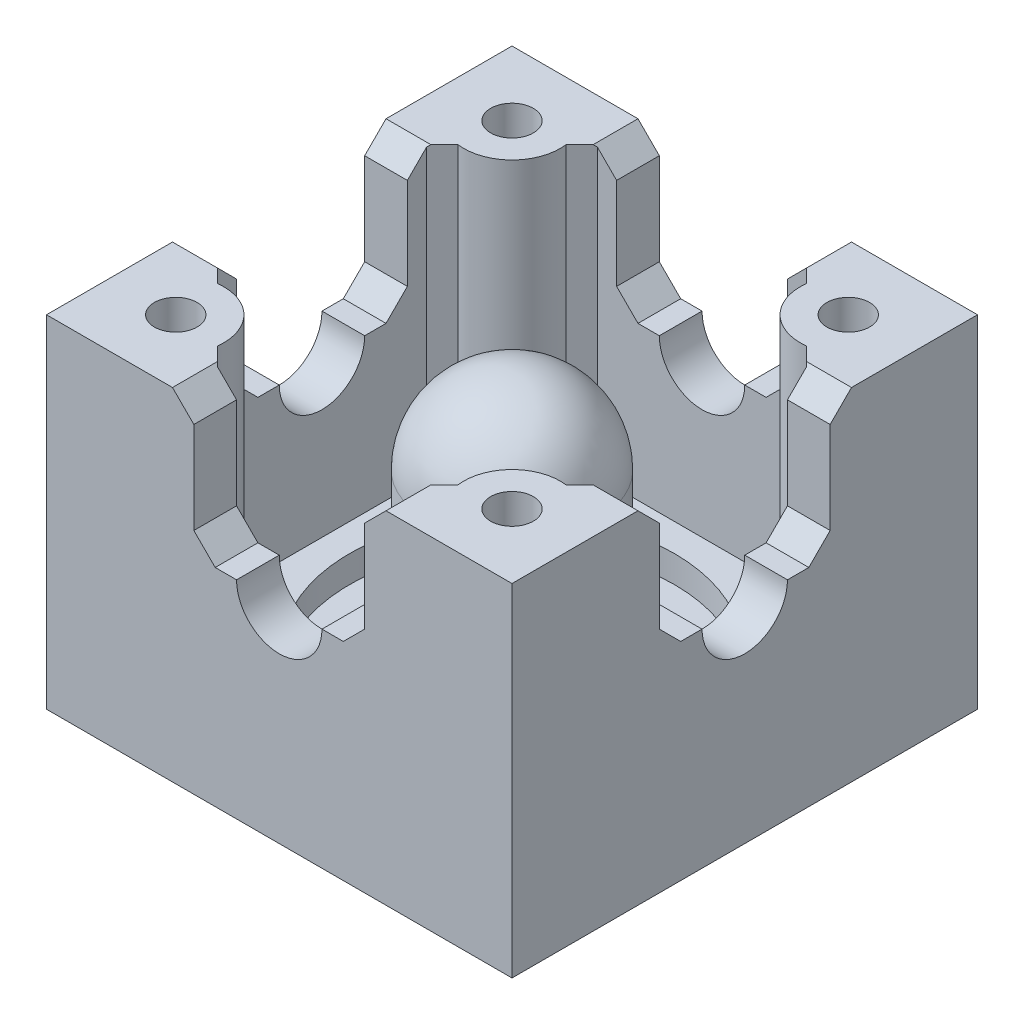
SolidWorks part; units mm, degrees
ref_plane "Front Plane" through (0, 0, 0) normal (0, 0, 1) x (1, 0, 0)
ref_plane "Top Plane" through (0, 0, 0) normal (0, 1, 0) x (1, 0, 0)
ref_plane "Right Plane" through (0, 0, 0) normal (1, 0, 0) x (0, 0, -1)
sketch "Sketch1" plane through (0, 0, 0) normal (0, 1, 0) x (1, 0, 0)
  line L1 (0, 0) -> (13.843, 0)
  line L2 (0, 0) -> (0, 13.843)
  line L3 (0, 13.843) -> (13.843, 13.843)
  line L4 (13.843, 0) -> (13.843, 13.843)
  dimension "D1" = 13.843
  dimension "D2" = 13.843
extrude "main body extrude" add sketch "Sketch1" along normal blind 10.16
sketch "Sketch4" plane through (0, 10.16, 0) normal (0, 1, 0) x (1, 0, 0)
  line L0 (0, 13.843) -> (13.843, 0) construction
  line L1 (13.843, 0) -> (13.843, 13.843) construction
  line L2 (1.27, 10.033) -> (3.81, 12.573)
  line L7 (13.843, 13.843) -> (0, 13.843) construction
  line L8 (3.81, 1.27) -> (10.033, 1.27)
  line L9 (10.033, 12.573) -> (12.573, 10.033)
  line L10 (0, 0) -> (13.843, 0) construction
  line L15 (1.27, 3.81) -> (1.27, 10.033)
  line L16 (3.81, 12.573) -> (10.033, 12.573)
  line L17 (12.573, 3.81) -> (12.573, 10.033)
  line L18 (1.27, 1.27) -> (12.573, 12.573) construction
  line L19 (1.27, 12.573) -> (12.573, 1.27) construction
  line L20 (10.033, 1.27) -> (12.573, 3.81)
  line L21 (1.27, 3.81) -> (3.81, 1.27)
  circle A0 centre (1.9215, 11.9215) radius 0.635
  circle A1 centre (11.9215, 11.9215) radius 0.635
  circle A2 centre (11.9215, 1.9215) radius 0.635
  circle A3 centre (1.9215, 1.9215) radius 0.635
  circle A4 centre (1.9215, 11.9215) radius 1.435
  circle A5 centre (11.9215, 11.9215) radius 1.435
  circle A6 centre (11.9215, 1.9215) radius 1.435
  circle A7 centre (1.9215, 1.9215) radius 1.435
  point P5 (6.9215, 6.9215)
  point P6 (6.9215, 6.9215)
  point P27 (6.9215, 6.9215)
  point P28 (6.9215, 6.9215)
  point P44 (6.9215, 6.9215)
  dimension "D3" = 1.27
  dimension "D6" = 0.8
  dimension "D1" = 1.27
  dimension "D2" = 1.27
  dimension "D5" = 10
  dimension "D4" = 4
  dimension "D7" = 4
extrude "main body cut" cut sketch "Sketch4" against normal offset from surface (9.36 mm away) 0.8 contours L8 region at (6.9215, 10.16, -6.9215) up to face at (6.9215, 0, -6.9215)
sketch "Sketch21" plane through (0, 10.16, 0) normal (0, 1, 0) x (1, 0, 0)
  line L0 (0, 13.843) -> (13.843, 0) construction
  circle A0 centre (1.9215, 11.9215) radius 0.635
  circle A1 centre (11.9215, 11.9215) radius 0.635
  circle A2 centre (11.9215, 1.9215) radius 0.635
  circle A3 centre (1.9215, 1.9215) radius 0.635
  point P7 (6.9215, 6.9215)
  point P17 (6.9215, 6.9215)
  dimension "D2" = 1.27
  dimension "D1" = 4
extrude "screw holes cut" cut sketch "Sketch21" against normal through all
sketch "Sketch5" plane through (0, 0, 0) normal (0, 0, 1) x (1, 0, 0)
  line L0 (6.9215, 12.7116) -> (6.9215, 6.1595) construction
  line L1 (8.1915, 12.7116) -> (8.1915, 6.1595)
  line L2 (0, 10.16) -> (13.843, 10.16) construction
  line L3 (5.6515, 12.7116) -> (5.6515, 6.1595)
  line L4 (6.9215, 6.1595) -> (6.9215, 2.6781) construction
  line L5 (4.3815, 12.7116) -> (9.4615, 12.7116)
  line L6 (4.3815, 12.7116) -> (4.3815, 6.1595)
  line L7 (4.3815, 6.1595) -> (9.4615, 6.1595)
  line L8 (9.4615, 12.7116) -> (9.4615, 6.1595)
  line L9 (4.3815, 12.7116) -> (9.4615, 6.1595) construction
  line L10 (4.3815, 6.1595) -> (9.4615, 12.7116) construction
  line L19 (11.811, 5.207) -> (10.541, 5.207)
  line L20 (2.032, 8.509) -> (3.302, 8.509)
  line L21 (2.032, 8.509) -> (2.032, 5.207)
  line L22 (2.032, 5.207) -> (3.302, 5.207)
  line L23 (3.302, 8.509) -> (3.302, 5.207)
  line L24 (10.541, 8.509) -> (10.541, 5.207)
  line L25 (11.811, 8.509) -> (10.541, 8.509)
  line L26 (11.811, 8.509) -> (11.811, 5.207)
  arc A1 (8.1915, 12.7116) -> (5.6515, 12.7116) centre (6.9215, 12.7116) ccw
  arc A2 (5.6515, 6.1595) -> (8.1915, 6.1595) centre (6.9215, 6.1595) ccw
  circle A3 centre (6.9215, 6.1595) radius 1.27 construction
  point P2 (6.9215, 10.16)
  point P3 (6.9215, 9.4356)
  point P14 (6.9215, 9.4356)
  line M8 (13.843, 10.16) -> (0, 10.16)
  dimension "D1" = 2.54
  dimension "D2" = 4.0005
  dimension "D3" = 5.08
  dimension "D4" = 1.27
  dimension "D5" = 3.302
  dimension "D6" = 7.239
  dimension "D7" = 1.651
extrude "x axis slot" cut sketch "Sketch5" against normal through all contours L6 L7 L3 M8 | L3 L7 L1 M8 | L8 L1 L7 M8 | L7 A2 region at (8.8265, 8.1598, 0) region at (6.9215, 8.1598, 0) region at (6.9215, 5.6205, 0) region at (5.0165, 8.1598, 0)
sketch "Sketch6" plane through (13.843, 0, 0) normal (1, 0, 0) x (0, 0, -1)
  line L0 (0, 10.16) -> (13.843, 10.16) construction
  line L1 (6.9215, 6.1595) -> (6.9215, 12.6452) construction
  line L2 (5.6515, 6.1595) -> (5.6515, 12.6452)
  line L3 (8.1915, 6.1595) -> (8.1915, 12.6452)
  line L4 (6.9215, 6.1595) -> (6.9215, 2.9038) construction
  line L5 (4.3815, 12.6452) -> (9.4615, 12.6452)
  line L6 (4.3815, 12.6452) -> (4.3815, 6.1595)
  line L7 (4.3815, 6.1595) -> (9.4615, 6.1595)
  line L8 (9.4615, 12.6452) -> (9.4615, 6.1595)
  line L9 (4.3815, 12.6452) -> (9.4615, 6.1595) construction
  line L10 (4.3815, 6.1595) -> (9.4615, 12.6452) construction
  circle A0 centre (6.9215, 6.1595) radius 1.27 construction
  arc A1 (5.6515, 6.1595) -> (8.1915, 6.1595) centre (6.9215, 6.1595) ccw
  arc A2 (8.1915, 12.6452) -> (5.6515, 12.6452) centre (6.9215, 12.6452) ccw
  point P6 (6.9215, 10.16)
  point P7 (6.9215, 9.4024)
  point P13 (6.9215, 7.4295)
  point P15 (6.9215, 9.4024)
  line M8 (13.843, 10.16) -> (0, 10.16)
  dimension "D1" = 2.54
  dimension "D2" = 4.0005
  dimension "D3" = 5.08
extrude "y axis slot" cut sketch "Sketch6" against normal through all contours L6 L7 L2 M8 | L2 L7 L3 M8 | L7 A1 | L8 L3 L7 M8 region at (13.843, 8.1598, -5.0165) region at (13.843, 8.1598, -6.9215) region at (13.843, 5.6205, -6.9215) region at (13.843, 8.1598, -8.8265)
sketch "Sketch11" plane through (0, 0.8, 0) normal (0, 1, 0) x (1, 0, 0)
  line L0 (1.27, 12.573) -> (12.573, 1.27) construction
  line L1 (12.573, 12.573) -> (1.27, 1.27) construction
  line L3 (1.27, 12.573) -> (12.573, 12.573)
  line L4 (1.27, 12.573) -> (1.27, 1.27)
  line L5 (1.27, 1.27) -> (12.573, 1.27)
  line L6 (12.573, 12.573) -> (12.573, 1.27)
  line L9 (3.81, 12.573) -> (4.3815, 12.573) construction
  line L10 (1.27, 9.4615) -> (1.27, 10.033) construction
  line L12 (3.81, 1.27) -> (4.3815, 1.27) construction
  circle A0 centre (6.9215, 6.9215) radius 4.826
  point P2 (12.643, 12.643)
  point P3 (12.4847, 2.5422)
  point P6 (11.7339, 13.4183)
  point P7 (3.6106, 11.4933)
  point P14 (12.573, 1.27)
  dimension "D1" = 9.652
extrude "spring retainer extrude" add sketch "Sketch11" along normal blind 0.8
sketch "Sketch12" plane through (0, 0.8, 0) normal (0, 1, 0) x (1, 0, 0)
  line L0 (0, 13.843) -> (13.843, 0) construction
  circle A0 centre (6.9215, 6.9215) radius 2.54
  dimension "D1" = 5.08
extrude "Stick support" add sketch "Sketch12" along normal up to vertex (5.3595 mm away) up to point (5.6515, 6.1595, -1.27)
sketch "Sketch20" plane through (0, 6.1595, 0) normal (0, 1, 0) x (1, 0, 0)
  circle A0 centre (6.9215, 6.9215) radius 2.54
  circle A1 centre (6.9215, 6.9215) radius 2.54 construction
extrude "Boss-Extrude9" add sketch "Sketch20" along normal blind 2.54
fillet "Fillet4" radius 2.54 1 edges at (6.9215, 8.6995, -4.3815)
sketch "Sketch16" [suppressed] plane through (0, 10.16, 0) normal (0, 1, 0) x (1, 0, 0)
  line L0 (1.2, 10.103) -> (3.74, 12.643)
  line L1 (1.2, 12.643) -> (1.2, 1.2) construction
  line L2 (12.643, 12.643) -> (1.2, 12.643) construction
  line L3 (1.2, 10.103) -> (1.2, 12.643)
  line L4 (1.2, 12.643) -> (3.74, 12.643)
  line L5 (0, 13.843) -> (13.843, 0) construction
  line L6 (10.103, 12.643) -> (12.643, 10.103)
  line L7 (12.643, 12.643) -> (12.643, 10.103)
  line L8 (10.103, 12.643) -> (12.643, 12.643)
  line L9 (12.643, 3.74) -> (10.103, 1.2)
  line L10 (12.643, 1.2) -> (10.103, 1.2)
  line L11 (12.643, 3.74) -> (12.643, 1.2)
  line L12 (3.74, 1.2) -> (1.2, 3.74)
  line L13 (1.2, 1.2) -> (1.2, 3.74)
  line L14 (3.74, 1.2) -> (1.2, 1.2)
  point P12 (6.9215, 6.9215)
  point P25 (6.9215, 6.9215)
  dimension "D1" = 2.54
  dimension "D2" = 2.54
  dimension "D3" = 4
extrude "screw extrude 1" [suppressed] add sketch "Sketch16" against normal up to surface (8.56 mm away) up to face at (6.9215, 1.6, -2.0955)
sketch "Sketch15" [suppressed] plane through (0, 10.16, 0) normal (0, 1, 0) x (1, 0, 0)
  line L0 (0, 13.843) -> (13.843, 0) construction
  circle A0 centre (1.9215, 11.9215) radius 0.635
  circle A1 centre (11.9215, 11.9215) radius 0.635
  circle A2 centre (11.9215, 1.9215) radius 0.635
  circle A3 centre (1.9215, 1.9215) radius 0.635
  point P4 (6.9215, 6.9215)
  point P16 (6.9215, 6.9215)
  dimension "D1" = 1.27
  dimension "D3" = 10
  dimension "D2" = 4
extrude "screw cut 2" [suppressed] cut sketch "Sketch15" against normal through all
sketch "Sketch17" [suppressed] plane through (0, 10.16, 0) normal (0, 1, 0) x (1, 0, 0)
  line L0 (0, 13.843) -> (13.843, 0) construction
  circle A0 centre (1.9215, 11.9215) radius 1.143
  circle A1 centre (11.9215, 11.9215) radius 1.143
  circle A2 centre (11.9215, 1.9215) radius 1.143
  circle A3 centre (1.9215, 1.9215) radius 1.143
  circle A4 centre (1.9215, 11.9215) radius 0.635 construction
  circle A5 centre (1.9215, 11.9215) radius 0.635
  circle A6 centre (11.9215, 11.9215) radius 0.635
  circle A7 centre (11.9215, 1.9215) radius 0.635
  circle A8 centre (1.9215, 1.9215) radius 0.635
  point P7 (6.9215, 6.9215)
  point P17 (6.9215, 6.9215)
  point P27 (6.9215, 6.9215)
  dimension "D2" = 0.508
  dimension "D1" = 4
  dimension "D3" = 4
extrude "screw extrude 2" [suppressed] add sketch "Sketch17" against normal up to surface (8.56 mm away) up to face at (6.9215, 1.6, -2.0955)
sketch "Sketch9" plane through (0, 0, 0) normal (0, -1, 0) x (1, 0, 0)
  line L0 (6.9215, 0) -> (6.9215, -13.843) construction
  line L1 (0, 0) -> (13.843, 0) construction
  line L2 (13.843, -13.843) -> (0, -13.843) construction
  line L3 (0, -6.9215) -> (13.843, -6.9215) construction
  line L4 (0, -13.843) -> (0, 0) construction
  line L5 (13.843, 0) -> (13.843, -13.843) construction
  circle A0 centre (6.9215, -1.8415) radius 0.625
  circle A1 centre (6.9215, -12.0015) radius 0.625
  dimension "D1" = 1.25
  dimension "D2" = 10.16
extrude "mounting holes 1 cut " [suppressed] cut sketch "Sketch9" against normal blind 2.54
chamfer "Chamfer1" distance 0.635 angle 45 16 edges at (0.635, 10.16, -9.4615) (0.635, 6.1595, -9.4615) (0.635, 6.1595, -4.3815) (0.635, 10.16, -4.3815) (9.4615, 10.16, -0.635) (9.4615, 6.1595, -0.635) (4.3815, 6.1595, -0.635) (4.3815, 10.16, -0.635) (13.208, 10.16, -4.3815) (13.208, 6.1595, -4.3815) (13.208, 6.1595, -9.4615) (13.208, 10.16, -9.4615) (9.4615, 10.16, -13.208) (9.4615, 6.1595, -13.208) (4.3815, 6.1595, -13.208) (4.3815, 10.16, -13.208)
